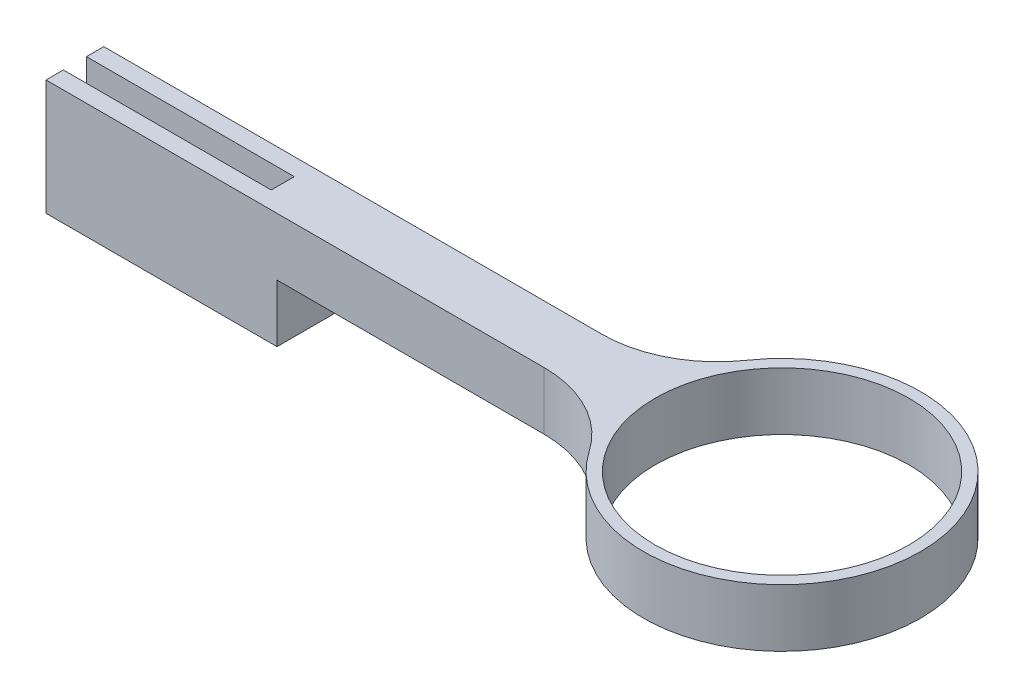
SolidWorks part; units mm, degrees
ref_plane "Спереди" through (0, 0, 0) normal (0, 0, 1) x (1, 0, 0)
ref_plane "Сверху" through (0, 0, 0) normal (0, 1, 0) x (1, 0, 0)
ref_plane "Справа" through (0, 0, 0) normal (1, 0, 0) x (0, 0, -1)
sketch "Эскиз1" plane through (0, 0, 0) normal (0, 1, 0) x (1, 0, 0)
  circle A0 centre (0, 0) radius 11
  circle A1 centre (0, 0) radius 12
  dimension "D1" = 22
  dimension "D2" = 24
extrude "ring" add sketch "Эскиз1" along normal blind 5
sketch "Эскиз2" plane through (0, 0, 0) normal (0, 1, 0) x (1, 0, 0)
  line L0 (34.0214, 0) -> (-42.1067, 0) construction
  line L2 (-11.225, 2.5) -> (-61.225, 2.5)
  line L3 (-11.225, 2.5) -> (-11.225, -2.5)
  line L4 (-11.225, -2.5) -> (-61.225, -2.5)
  line L5 (-61.225, 2.5) -> (-61.225, -2.5)
  circle A0 centre (0, 0) radius 11.5 construction
  dimension "D3" = 23
  dimension "D1" = 2.5
  dimension "D2" = 5
  dimension "D4" = 50
extrude "stick" add sketch "Эскиз2" along normal blind 5
sketch "Эскиз3" plane through (0, 0, 0) normal (0, 1, 0) x (1, 0, 0)
  line L0 (-61.225, -2.5) -> (-11.7367, -2.5) construction
  line L1 (-61.225, 2.5) -> (-41.225, 2.5)
  line L2 (-61.225, 2.5) -> (-61.225, -2.5)
  line L3 (-61.225, -2.5) -> (-41.225, -2.5)
  line L4 (-41.225, 2.5) -> (-41.225, -2.5)
  dimension "D1" = 20
extrude "key" add sketch "Эскиз3" against normal blind 5
sketch "Эскиз5" plane through (-61.225, 0, 0) normal (-1, 0, 0) x (0, 0, 1)
  line L0 (-2.5, -5) -> (2.5, -5) construction
  line L1 (-1, -5) -> (1, -5)
  line L2 (-1, -5) -> (-1, 5)
  line L3 (-1, 5) -> (1, 5)
  line L4 (1, -5) -> (1, 5)
  line L5 (-2.5, 5) -> (2.5, 5) construction
  dimension "D2" = 2
  dimension "D3" = 1.5
fillet "Скругление1" radius 10 2 edges at (-11.7367, 2.5, 2.5) (-11.7367, 2.5, -2.5)
extrude "slot" cut sketch "Эскиз5" against normal blind 18
